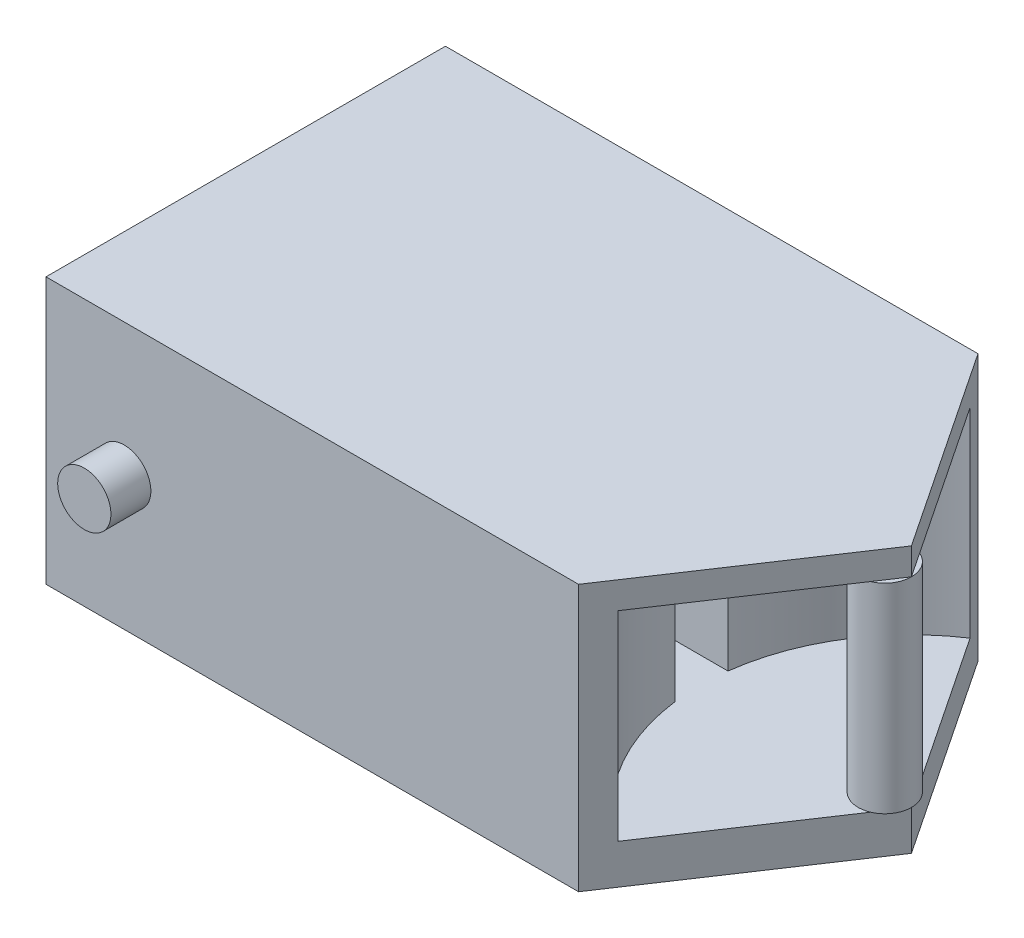
SolidWorks part; units mm, degrees
material "1023 Carbon Steel Sheet (SS)"
ref_plane "Front Plane" through (0, 0, 0) normal (0, 0, 1) x (1, 0, 0)
ref_plane "Top Plane" through (0, 0, 0) normal (0, 1, 0) x (1, 0, 0)
ref_plane "Right Plane" through (0, 0, 0) normal (1, 0, 0) x (0, 0, -1)
sketch "Sketch1" plane through (0, 0, 0) normal (0, 1, 0) x (1, 0, 0)
  line L0 (200, 150) -> (300, 0)
  line L1 (-200, 150) -> (200, 150)
  line L2 (-200, 150) -> (-200, -150)
  line L3 (-200, -150) -> (200, -150)
  line L5 (-200, 150) -> (200, -150) construction
  line L6 (-200, -150) -> (200, 150) construction
  line L7 (300, 0) -> (200, -150)
  point P0 (0, 0)
  point P7 (300, 0)
  dimension "D1" = 400
  dimension "D2" = 300
  dimension "D3" = 300
extrude "Boss-Extrude1" add sketch "Sketch1" along normal blind 100 and the other way blind 100
sketch "Sketch2" plane through (207.6923, 0, -138.4615) normal (0.8321, 0, -0.5547) x (-0.5547, 0, -0.8321)
  line L1 (-142.567, 79.8603) -> (-7.567, 79.8603)
  line L2 (-142.567, 79.8603) -> (-142.567, -70.1397)
  line L3 (-142.567, -70.1397) -> (-7.567, -70.1397)
  line L4 (-7.567, 79.8603) -> (-7.567, -70.1397)
  line L5 (-142.567, 79.8603) -> (-7.567, -70.1397) construction
  line L6 (-142.567, -70.1397) -> (-7.567, 79.8603) construction
  point P0 (-75.067, 4.8603)
  dimension "D1" = 135
  dimension "D2" = 150
revolve "Cut-Revolve1" cut sketch "Sketch2" angle 112.62 about axis through (300, -100, 0) along (0, 1, 0)
sketch "Sketch3" plane through (0, 0, -150) normal (0, 0, -1) x (-1, 0, 0)
  circle A0 centre (141.2295, 0) radius 20
  point P3 (121.2295, 0)
  dimension "D1" = 20
extrude "Boss-Extrude3" add sketch "Sketch3" along normal blind 30
ref_axis "Axis1" through (300, 100, 0) along (0, -1, 0)
ref_axis "Axis2" through (300, 100, 0) along (-1, 0, 0)
ref_plane "Plane1" through (0, 0, 0) normal (0, 0, -1) x (-1, 0, 0)
mirror "Mirror1" about plane through (0, 0, 0) normal (0, 0, -1) of "Boss-Extrude3"
sketch "Sketch4" plane through (-200, 0, 0) normal (-1, 0, 0) x (0, 0, 1)
  line L1 (19.8387, 79.8603) -> (-19.8387, 79.8603)
  line L2 (19.8387, 79.8603) -> (19.8387, -70.1397)
  line L4 (-19.8387, 79.8603) -> (-19.8387, -70.1397)
  line L7 (19.8387, -70.1397) -> (-19.8387, -70.1397)
  dimension "D1" = 39.6773
extrude "Cut-Extrude2" cut sketch "Sketch4" against normal blind 500
sketch "Sketch7" plane through (0, 0, 0) normal (0, 0, -1) x (-1, 0, 0)
  line L0 (-300, -70.1397) -> (-211.8897, -70.1397) construction
  line L1 (-300, 79.8603) -> (-280, 79.8603)
  line L2 (-300, 79.8603) -> (-300, -70.1397)
  line L3 (-300, -70.1397) -> (-280, -70.1397)
  line L4 (-280, 79.8603) -> (-280, -70.1397)
  dimension "D1" = 20
revolve "Revolve2" add sketch "Sketch7" angle 360 about L4
